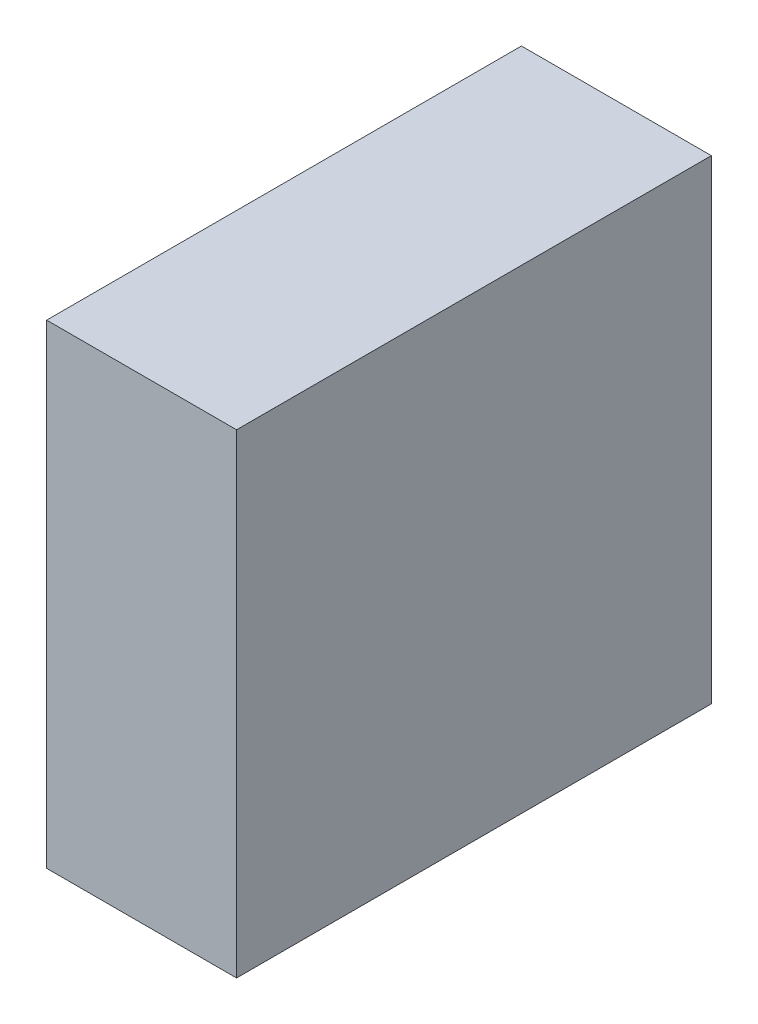
SolidWorks part; units mm, degrees
material "6061 Alloy"
ref_plane "Front Plane" through (0, 0, 0) normal (0, 0, 1) x (1, 0, 0)
ref_plane "Top Plane" through (0, 0, 0) normal (0, 1, 0) x (1, 0, 0)
ref_plane "Right Plane" through (0, 0, 0) normal (1, 0, 0) x (0, 0, -1)
sketch "Sketch1" plane through (0, 0, 0) normal (0, 0, 1) x (1, 0, 0)
  line L1 (-12.7, 31.75) -> (12.7, 31.75)
  line L2 (-12.7, 31.75) -> (-12.7, -31.75)
  line L3 (-12.7, -31.75) -> (12.7, -31.75)
  line L4 (12.7, 31.75) -> (12.7, -31.75)
  line L5 (-12.7, 31.75) -> (12.7, -31.75) construction
  line L6 (-12.7, -31.75) -> (12.7, 31.75) construction
  point P0 (0, 0)
  dimension "D1" = 63.5
  dimension "D2" = 25.4
extrude "Boss-Extrude1" add sketch "Sketch1" along normal blind 63.5
